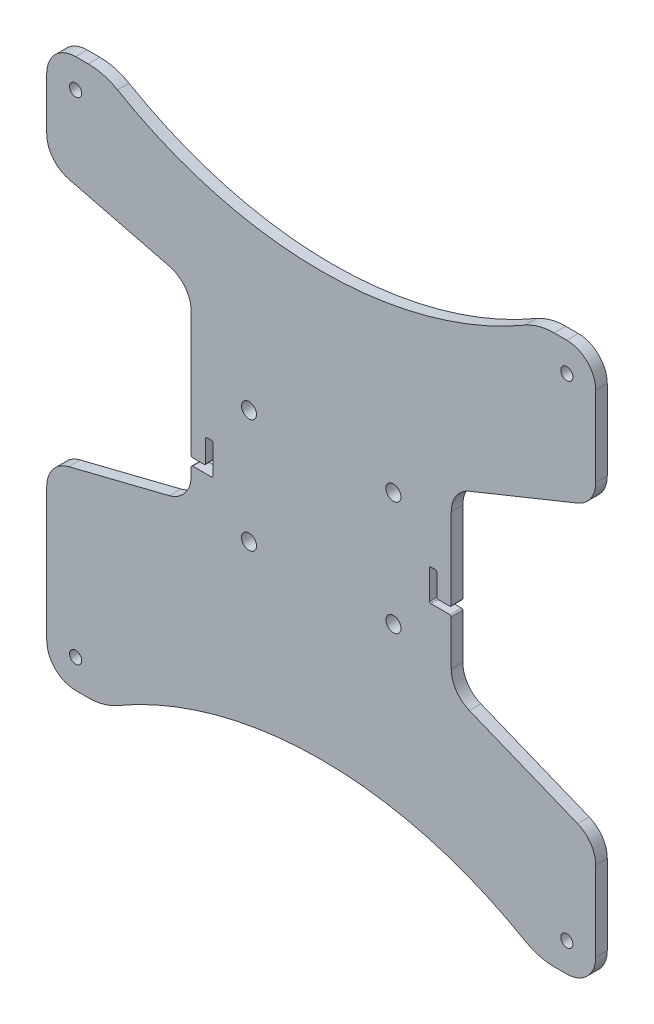
SolidWorks part; units mm, degrees
ref_plane "Front Plane" through (0, 0, 0) normal (0, 0, 1) x (1, 0, 0)
ref_plane "Top Plane" through (0, 0, 0) normal (0, 1, 0) x (1, 0, 0)
ref_plane "Right Plane" through (0, 0, 0) normal (1, 0, 0) x (0, 0, -1)
ref_plane "Plane1" through (0, 0, 0) normal (0, 0, -1) x (-1, 0, 0)
sketch "Sketch1" plane through (0, 0, 0) normal (0, 0, -1) x (-1, 0, 0)
  line L0 (87.4254, -29.1063) -> (52.5746, -20.3937)
  line L1 (45, -10.6922) -> (45, -8)
  line L2 (44.5, -7.5) -> (38, -7.5)
  line L3 (37.5, -7) -> (37.5, 3)
  line L4 (38, 3.5) -> (39.5, 3.5)
  line L5 (40, 3) -> (40, -4.5)
  line L6 (40.5, -5) -> (44.5, -5)
  line L7 (45, -4.5) -> (45, 38.6922)
  line L8 (52.5746, 48.3937) -> (87.4254, 57.1063)
  line L9 (95, 66.8078) -> (95, 85)
  line L10 (85, 95) -> (80.6, 95)
  line L11 (-80.6, 95) -> (-85, 95)
  line L12 (-95, 85) -> (-95, 57.3099)
  line L13 (-88.7544, 48.0415) -> (-51.2456, 32.8477)
  line L14 (-45, 23.5792) -> (-45, -4.5)
  line L15 (-44.5, -5) -> (-40.5, -5)
  line L16 (-40, -4.5) -> (-40, 3)
  line L17 (-39.5, 3.5) -> (-38, 3.5)
  line L18 (-37.5, 3) -> (-37.5, -7)
  line L19 (-38, -7.5) -> (-44.5, -7.5)
  line L20 (-45, -8) -> (-45, -23.5792)
  line L21 (-51.2456, -32.8477) -> (-88.7544, -48.0415)
  line L22 (-95, -57.3099) -> (-95, -85)
  line L23 (-85, -95) -> (-80.6, -95)
  line L24 (80.6, -95) -> (85, -95)
  line L25 (95, -85) -> (95, -38.8078)
  circle A0 centre (-85, -85) radius 2.1
  circle A1 centre (-85, 85) radius 2.1
  circle A2 centre (85, 85) radius 2.1
  circle A3 centre (85, -85) radius 2.1
  circle A4 centre (25, 19.0063) radius 2.6
  circle A5 centre (25, -20.3937) radius 2.6
  circle A6 centre (-25, -20.1) radius 2.6
  circle A7 centre (-25, 19.3) radius 2.6
  arc A8 (52.5746, -20.3937) -> (45, -10.6922) centre (55, -10.6922) cw
  arc A9 (45, -8) -> (44.5, -7.5) centre (44.5, -8) ccw
  arc A10 (38, -7.5) -> (37.5, -7) centre (38, -7) cw
  arc A11 (37.5, 3) -> (38, 3.5) centre (38, 3) cw
  arc A12 (39.5, 3.5) -> (40, 3) centre (39.5, 3) cw
  arc A13 (40, -4.5) -> (40.5, -5) centre (40.5, -4.5) ccw
  arc A14 (44.5, -5) -> (45, -4.5) centre (44.5, -4.5) ccw
  arc A15 (45, 38.6922) -> (52.5746, 48.3937) centre (55, 38.6922) cw
  arc A16 (87.4254, 57.1063) -> (95, 66.8078) centre (85, 66.8078) ccw
  arc A17 (95, 85) -> (85, 95) centre (85, 85) ccw
  arc A18 (80.6, 95) -> (70.525, 92.277) centre (80.6, 75) ccw
  arc A19 (70.525, 92.277) -> (-70.525, 92.277) centre (0, 213.2159) cw
  arc A20 (-70.525, 92.277) -> (-80.6, 95) centre (-80.6, 75) ccw
  arc A21 (-85, 95) -> (-95, 85) centre (-85, 85) ccw
  arc A22 (-95, 57.3099) -> (-88.7544, 48.0415) centre (-85, 57.3099) ccw
  arc A23 (-51.2456, 32.8477) -> (-45, 23.5792) centre (-55, 23.5792) cw
  arc A24 (-45, -4.5) -> (-44.5, -5) centre (-44.5, -4.5) ccw
  arc A25 (-40.5, -5) -> (-40, -4.5) centre (-40.5, -4.5) ccw
  arc A26 (-40, 3) -> (-39.5, 3.5) centre (-39.5, 3) cw
  arc A27 (-38, 3.5) -> (-37.5, 3) centre (-38, 3) cw
  arc A28 (-37.5, -7) -> (-38, -7.5) centre (-38, -7) cw
  arc A29 (-44.5, -7.5) -> (-45, -8) centre (-44.5, -8) ccw
  arc A30 (-45, -23.5792) -> (-51.2456, -32.8477) centre (-55, -23.5792) cw
  arc A31 (-88.7544, -48.0415) -> (-95, -57.3099) centre (-85, -57.3099) ccw
  arc A32 (-95, -85) -> (-85, -95) centre (-85, -85) ccw
  arc A33 (-80.6, -95) -> (-70.525, -92.277) centre (-80.6, -75) ccw
  arc A34 (-70.525, -92.277) -> (70.525, -92.277) centre (0, -213.2159) cw
  arc A35 (70.525, -92.277) -> (80.6, -95) centre (80.6, -75) ccw
  arc A36 (85, -95) -> (95, -85) centre (85, -85) ccw
  arc A37 (95, -38.8078) -> (87.4254, -29.1063) centre (85, -38.8078) ccw
  point P98 (-13, -20.1)
  point P99 (27, -20.3937)
  point P100 (-82.8, -95)
  dimension "D1" = 39.4
  dimension "D5" = 5.2
  dimension "D6" = 4.2
  dimension "D2" = 39.4
  dimension "D3" = 20
  dimension "D4" = 20
  dimension "D7" = 10
  dimension "D8" = 10
  dimension "D9" = 7.5
  dimension "D10" = 5
  dimension "D11" = 2.5
  dimension "D12" = 11
  dimension "D13" = 3.5
extrude "Boss-Extrude1" add sketch "Sketch1" against normal blind 4
